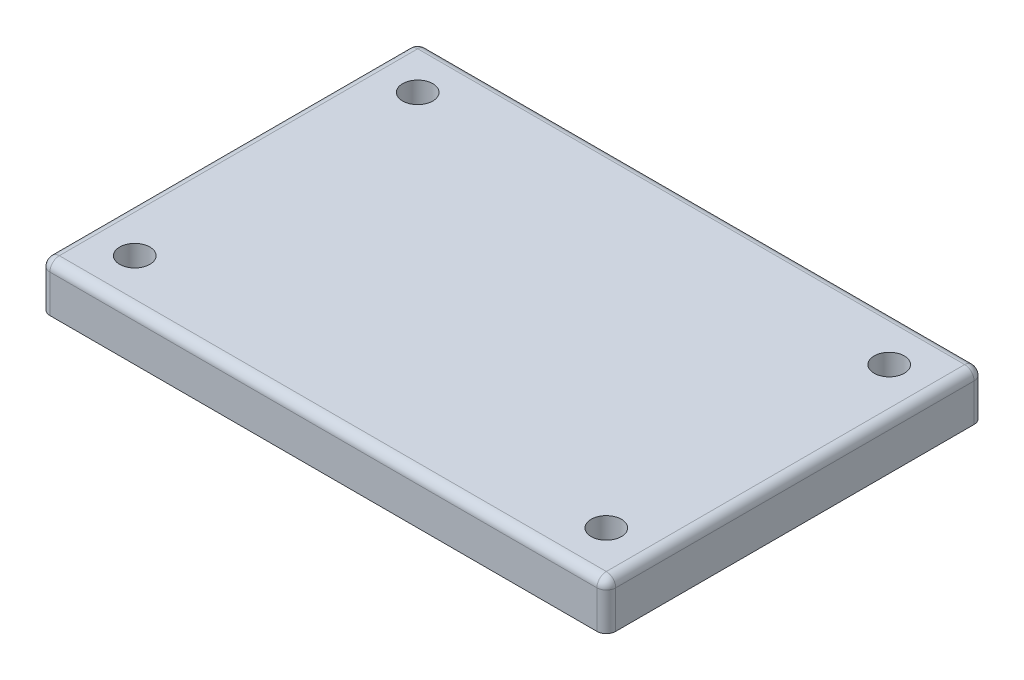
SolidWorks part; units mm, degrees
ref_plane "Front Plane" through (0, 0, 0) normal (0, 0, 1) x (1, 0, 0)
ref_plane "Top Plane" through (0, 0, 0) normal (0, 1, 0) x (1, 0, 0)
ref_plane "Right Plane" through (0, 0, 0) normal (1, 0, 0) x (0, 0, -1)
sketch "Sketch1" plane through (0, 0, 0) normal (0, 1, 0) x (1, 0, 0)
  line L1 (-30, 20) -> (30, 20)
  line L2 (-30, 20) -> (-30, -20)
  line L3 (-30, -20) -> (30, -20)
  line L4 (30, 20) -> (30, -20)
  line L5 (-30, 20) -> (30, -20) construction
  line L6 (-30, -20) -> (30, 20) construction
  point P0 (0, 0)
  dimension "D1" = 60
  dimension "D2" = 40
extrude "Boss-Extrude1" add sketch "Sketch1" along normal blind 5
sketch "Sketch2" plane through (0, 5, 0) normal (0, 1, 0) x (1, 0, 0)
  circle A1 centre (-25, 15) radius 1.6
  circle A3 centre (25, -15) radius 1.6
  circle A4 centre (-25, -15) radius 1.6
  circle A5 centre (25, 15) radius 1.6
  dimension "D1" = 3.2
extrude "Cut-Extrude1" cut sketch "Sketch2" against normal blind 5
fillet "Fillet1" radius 1 4 edges at (-30, 5, 0) (0, 5, -20) (30, 5, 0) (0, 5, 20)
fillet "Fillet2" radius 1 8 edges at (-29.7071, 4.7071, -19.7071) (29.7071, 4.7071, -19.7071) (29.7071, 4.7071, 19.7071) (-29.7071, 4.7071, 19.7071) (-30, 2, -20) (30, 2, -20) (30, 2, 20) (-30, 2, 20)
